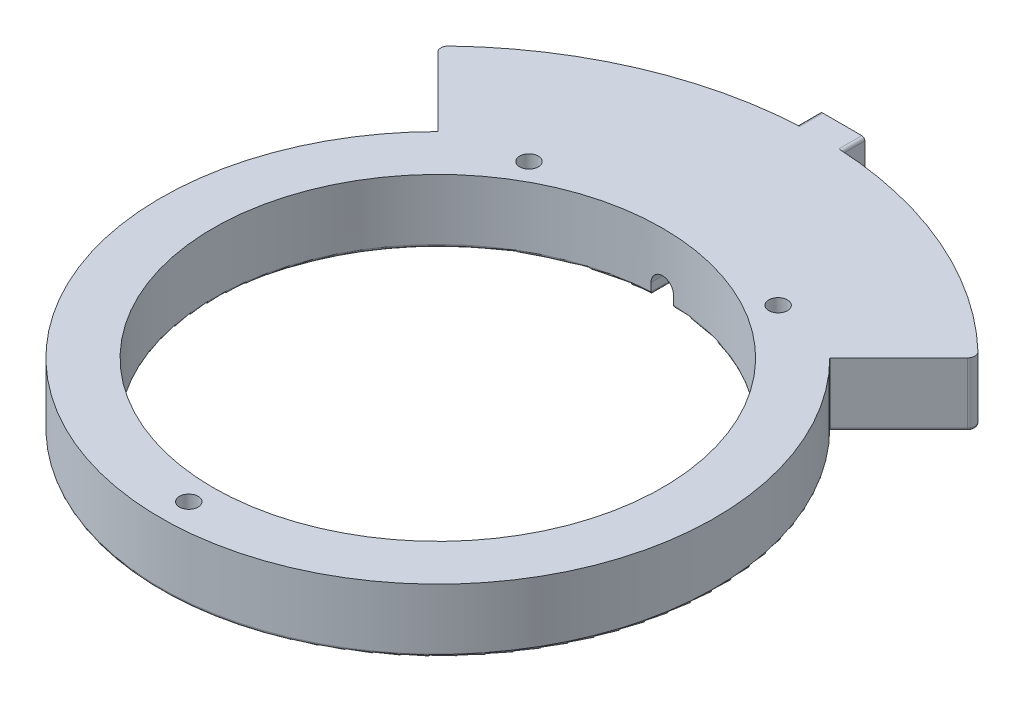
SolidWorks part; units mm, degrees
ref_plane "前视基准面" through (0, 0, 0) normal (0, 0, 1) x (1, 0, 0)
ref_plane "上视基准面" through (0, 0, 0) normal (0, 1, 0) x (1, 0, 0)
ref_plane "右视基准面" through (0, 0, 0) normal (1, 0, 0) x (0, 0, -1)
other "Configuration Table"
sketch "草图1" plane through (0, 0, 0) normal (0, 1, 0) x (1, 0, 0)
  circle A1 centre (0, 0) radius 37
  dimension "D2" = 74
extrude "凸台-拉伸1" add sketch "草图1" along normal blind 8.5
sketch "草图6" plane through (0, 0, 0) normal (1, 0, 0) x (0, 0, -1)
  line L0 (-37, 0) -> (37, 0) construction
  line L5 (37, 8.5) -> (51, 8.5)
  line L6 (37, 8.5) -> (37, 0)
  line L7 (37, 0) -> (51, 0)
  line L8 (51, 8.5) -> (51, 0)
  line L13 (0, 0) -> (0, 16.5886) construction
  line L15 (37, 0) -> (37, 8.5) construction
  dimension "D2" = 14
revolve "旋转1" add sketch "草图6" angle 45 about L13 region at (0, 4.25, -44) other way angle 45
sketch "草图9" plane through (0, 8.5, 0) normal (0, 1, 0) x (1, 0, 0)
  circle A0 centre (0, 0) radius 30
  dimension "D1" = 60
extrude "切除-拉伸7" cut sketch "草图9" against normal through all
sketch "草图12" plane through (0, 0, 0) normal (0, -1, 0) x (1, 0, 0)
  line L0 (-32.5, 0) -> (32.5, 0) construction
  circle A0 centre (32.5, 0) radius 1.25
  circle A1 centre (-32.5, 0) radius 1.25
  point P2 (0, 0)
  dimension "D1" = 2.5
  dimension "D2" = 65
extrude "切除-拉伸-固定灯" cut sketch "草图12" against normal blind 4
sketch "草图13" plane through (0, 0, 0) normal (0, -1, 0) x (1, 0, 0)
  line L0 (0, 0) -> (0, 33.25) construction
  line L1 (0, 0) -> (-16.625, -28.7953) construction
  line L2 (0, 0) -> (16.625, -28.7953) construction
  circle A0 centre (0, 33.25) radius 2.5
  circle A1 centre (-16.625, -28.7953) radius 2.5
  circle A2 centre (16.625, -28.7953) radius 2.5
  dimension "D3" = 5
  dimension "D1" = 30
  dimension "D2" = 30
  dimension "D4" = 33.25
extrude "切除-拉伸-固定面板-1" cut sketch "草图13" against normal offset from surface (5 mm away) 3.5 up to face at (0, 8.5, 30)
sketch "草图14" plane through (0, 5, 0) normal (0, -1, 0) x (1, 0, 0)
  circle A0 centre (0, 33.25) radius 1.25
  circle A1 centre (16.625, -28.7953) radius 1.25
  circle A2 centre (-16.625, -28.7953) radius 1.25
  dimension "D1" = 2.5
extrude "切除-拉伸-固定面板-2" cut sketch "草图14" against normal through all
ref_plane "基准面1" through (0, 0, -25) normal (0, 0, 1) x (1, 0, 0)
ref_plane "基准面2" through (0, 0, -48) normal (0, 0, 1) x (1, 0, 0)
sketch "草图16" plane through (0, 0, -48) normal (0, 0, 1) x (1, 0, 0)
  line L0 (-36.0624, 0) -> (36.0624, 0) construction
  line L1 (-3, 0) -> (3, 0)
  line L2 (-3, 0) -> (-3, 8.5)
  line L3 (-3, 8.5) -> (3, 8.5)
  line L4 (3, 0) -> (3, 8.5)
  line L5 (36.0624, 8.5) -> (-36.0624, 8.5) construction
  line L6 (36.0624, 8.5) -> (-36.0624, 8.5) construction
  point P6 (5.5638, 0)
  point P8 (0, 0)
  point P10 (2.9578, 7.902)
  point P11 (3.1174, 8.2211)
  point P12 (0, 0)
  point P13 (3, 7.3702)
  point P16 (3, 8.5)
  dimension "D1" = 6
extrude "凸台-拉伸2" add sketch "草图16" against normal blind 6
sketch "草图15" plane through (0, 0, -25) normal (0, 0, 1) x (1, 0, 0)
  line L2 (1.5, 0) -> (-1.5, 0)
  line L3 (1.5, 0) -> (1.5, 1.5)
  line L4 (-1.5, 0) -> (-1.5, 1.5)
  arc A0 (1.5, 1.5) -> (-1.5, 1.5) centre (0, 1.5) ccw
  point P18 (0, 0)
  dimension "D1" = 1.5
  dimension "D2" = 1.5
extrude "切除-拉伸8" cut sketch "草图15" against normal through all
fillet "圆角1" radius 1 2 edges at (-36.0624, 4.25, -36.0624) (36.0624, 4.25, -36.0624)
fillet "圆角2" radius 0.4 21 edges at (-32.5, 0, -1.25) (32.5, 0, -1.25) (16.625, 0, -31.2953) (-16.625, 0, -31.2953) (0, 0, 30.75) (0, 0, 37) (30.7556, 0, -30.7556) (35.6411, 0, -36.0654) (20.4285, 0, -46.7298) (3, 0, -52.4558) (2.25, 0, -54) (1.5, 0, -41.9812) (0, 0, 30) (-1.5, 0, -41.9812) (-2.25, 0, -54) (-3, 0, -52.4558) (-20.4285, 0, -46.7298) (-35.6411, 0, -36.0654) (-30.7556, 0, -30.7556) (-3, 8.5, -52.4558) (3, 8.5, -52.4558)
equation "\"border_size\"=4"
